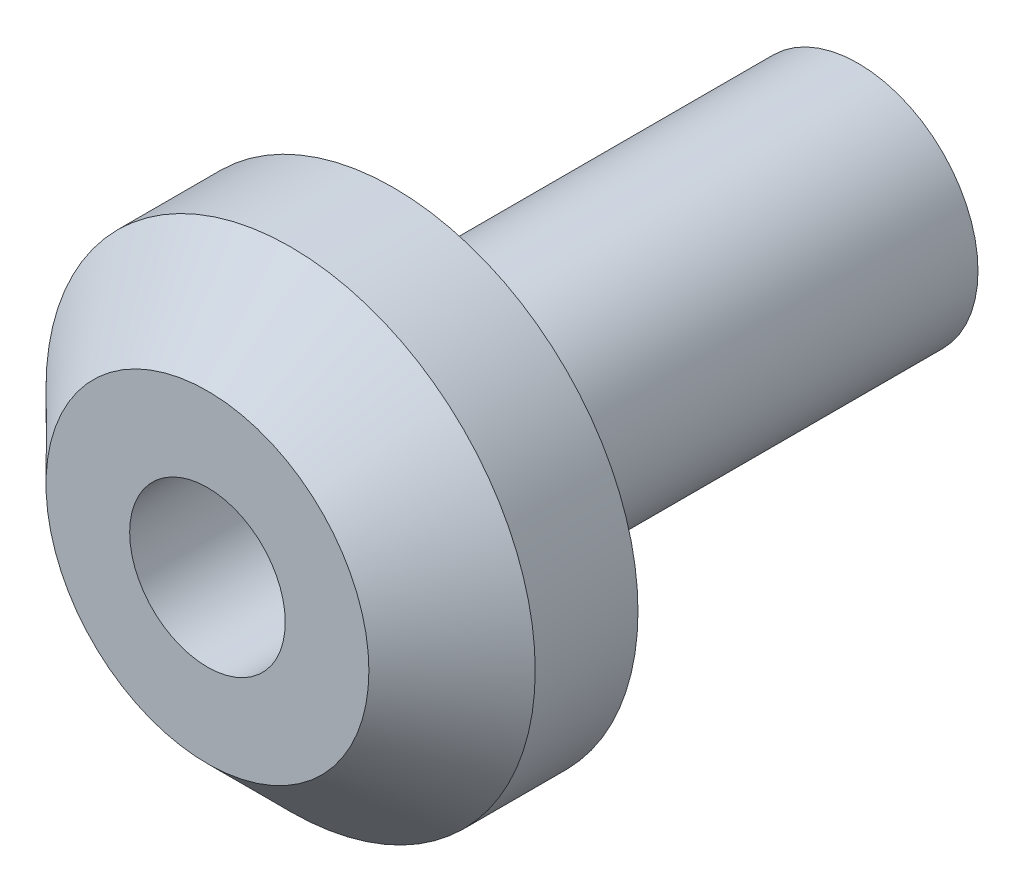
SolidWorks part; units mm, degrees
ref_plane "Front Plane" through (0, 0, 0) normal (0, 0, 1) x (1, 0, 0)
ref_plane "Top Plane" through (0, 0, 0) normal (0, 1, 0) x (1, 0, 0)
ref_plane "Right Plane" through (0, 0, 0) normal (1, 0, 0) x (0, 0, -1)
sketch "Sketch1" plane through (0, 0, 0) normal (0, 0, 1) x (1, 0, 0)
  circle A0 centre (0, 0) radius 4.0386
  circle A1 centre (0, 0) radius 12.7
extrude "Boss-Extrude1" add sketch "Sketch1" along normal blind 9.652
sketch "Sketch2" plane through (0, 0, 0) normal (0, 0, -1) x (-1, 0, 0)
  circle A0 centre (0, 0) radius 4.0386
  circle A1 centre (0, 0) radius 6.223
extrude "Boss-Extrude2" add sketch "Sketch2" along normal blind 24.13
chamfer "Chamfer1" distance 4.318 angle 45 1 edges at (12.7, 0, 9.652)
